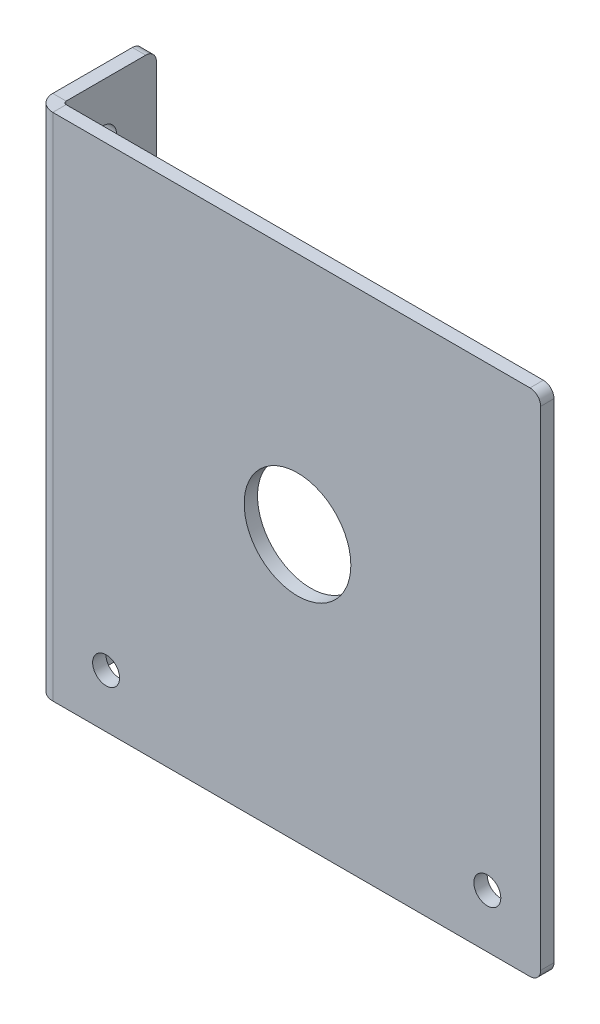
SolidWorks part; units mm, degrees
note: The reader was unsure of these and kept them because the rebuilt part matched: flange length of "Edge-Flange1".
ref_plane "Front Plane" through (0, 0, 0) normal (1, 0, 0) x (0, 1, 0)
ref_plane "Top Plane" through (0, 0, 0) normal (0, 0, 1) x (0, 1, 0)
ref_plane "Right Plane" through (0, 0, 0) normal (0, 1, 0) x (-1, 0, 0)
sketch "Sketch1" plane through (0, 0, 0) normal (0, 0, 1) x (0, 1, 0)
  line L0 (-32.5, 32.5) -> (-63.5, 32.5) construction
  line L1 (-63.5, 62.1879) -> (57.9, 62.1879)
  line L2 (-63.5, 62.1879) -> (-63.5, -57.9)
  line L3 (-63.5, -57.9) -> (57.9, -57.9)
  line L4 (57.9, 62.1879) -> (57.9, -57.9)
  line L5 (32.5, -32.5) -> (32.5, -57.9) construction
  line L6 (32.5, 32.5) -> (32.5, 57.9) construction
  line L7 (57.9, 57.9) -> (-63.5, 57.9) construction
  line L8 (0, 0) -> (32.5, 0) construction
  line L9 (-32.5, 32.5) -> (32.5, 32.5) construction
  line L11 (-32.5, -32.5) -> (32.5, -32.5) construction
  line L12 (32.5, 32.5) -> (32.5, -32.5) construction
  line L13 (-32.5, 32.5) -> (32.5, -32.5) construction
  line L14 (-32.5, -32.5) -> (32.5, 32.5) construction
  line L15 (-32.5, -32.5) -> (-63.5, -32.5) construction
  circle A0 centre (0, 0) radius 12.7
  point P0 (0, 0)
  dimension "D3" = 25.4
  dimension "D1" = 32.5
  dimension "D2" = 4.2879
  dimension "D4" = 63.5
  dimension "D5" = 25.4
  dimension "D6" = 25.4
  dimension "D7" = 25.4
base flange "Base-Flange1" sketch "Sketch1" thickness 3.175 reverse thickness direction yes parameters "D1"=0.7366
edge flange "Edge-Flange1" sketch "Sketch8" flange angle 90 flange length 25.4 flange position material inside bend radius 0.7366 thickness 3.175 relief rectangular parameters "D6"=10
sketch "Sketch8" plane through (-62.1879, 0, 0) normal (-1, 0, 0) x (0, 1, 0)
  line L0 (57.9, 0) -> (-63.5, 0) construction
  line L1 (57.9, 0) -> (-63.5, 0)
  line L2 (-63.5, 0) -> (-63.5, 22.225)
  line L3 (-63.5, 22.225) -> (57.9, 22.225)
  line L4 (57.9, 22.225) -> (57.9, 0)
bend "EdgeBend1" bend radius 0.7366 bend angle 90 parameters "D5"=1
fillet "Fillet1" radius 2.54 4 edges at (57.9, 57.9, 1.5875) (-60.6004, -63.5, -22.225) (-60.6004, 57.9, -22.225) (57.9, -63.5, 1.5875)
sketch "Sketch9" plane through (-59.0129, 0, 0) normal (1, 0, 0) x (0, 1, 0)
  line L0 (-38.1, -0.7366) -> (-38.1, -22.225) construction
  line L1 (-63.5, -0.7366) -> (57.9, -0.7366) construction
  line L4 (-25.4, -9.525) -> (-38.1, -9.525) construction
  line L8 (55.36, -22.225) -> (-60.96, -22.225) construction
  line L9 (45.2, -9.525) -> (57.9, -9.525) construction
  line L10 (57.9, -0.7366) -> (57.9, -19.685) construction
  line L12 (-63.5, -19.685) -> (-63.5, -0.7366) construction
  circle A0 centre (45.2, -9.525) radius 3.205
  circle A1 centre (-25.4, -9.525) radius 3.205
  dimension "D3" = 6.41
  dimension "D1" = 12.7
  dimension "D2" = 12.7
  dimension "D4" = 25.4
extrude "Lower T-Slot Holes" cut sketch "Sketch9" against normal through all normal cut yes
sketch "Sketch10" plane through (0, 0, 0) normal (0, 0, -1) x (1, 0, 0)
  line L0 (45.2, 50.8) -> (57.9, 50.8) construction
  line L2 (57.9, 60.96) -> (57.9, -55.36) construction
  line L4 (57.9, -55.36) -> (57.9, 60.96)
  line L5 (55.36, 63.5) -> (-58.2763, 63.5)
  line L6 (-58.2763, 63.5) -> (-58.2763, -57.9)
  line L7 (-58.2763, -57.9) -> (55.36, -57.9)
  line L8 (57.9, 22.1937) -> (57.9, 28.6063) construction
  line L10 (-58.2763, 28.6063) -> (-58.2763, 22.1937) construction
  line L12 (-45.5763, 50.8) -> (-58.2763, 50.8) construction
  line L13 (-58.2763, -57.9) -> (-58.2763, 63.5) construction
  line L14 (-45.5763, 50.8) -> (45.2, 50.8) construction
  line L15 (-58.2763, 63.5) -> (55.36, 63.5) construction
  circle A0 centre (-45.5763, 50.8) radius 3.2063
  circle A1 centre (45.2, 50.8) radius 3.2063
  arc A2 (57.9, 60.96) -> (55.36, 63.5) centre (55.36, 60.96) ccw
  arc A3 (55.36, -57.9) -> (57.9, -55.36) centre (55.36, -55.36) ccw
  dimension "D3" = 12.7
  dimension "D4" = 12.7
  dimension "D1" = 0
extrude "Upper T-Slot Holes" cut sketch "Sketch10" against normal through all normal cut yes
sketch "Bend-Lines1" [suppressed] plane through (0, 0, 0) normal (0, 1, 0) x (1, 0, 0)
sketch "Bounding-Box1" [suppressed] plane through (0, 0, 0) normal (0, 1, 0) x (1, 0, 0)
sheet metal parameters "Sheet-Metal1" thickness 3.175 parameters "D1"=0.7366
flat pattern "Flat-Pattern1" [suppressed]
sketch "Bend-Lines2" plane through (0, 0, 0) normal (0, 1, 0) x (1, 0, 0)
sketch3d "Bounding-Box2" [suppressed]
  line L0 (-38.1, -38.1, 0) -> (38.1, -38.1, 0) construction
  line L1 (-38.1, 38.1, 0) -> (38.1, 38.1, 0) construction
  line L2 (-38.1, -38.1, 0) -> (-38.1, 38.1, 0) construction
  line L3 (38.1, -38.1, 0) -> (38.1, 38.1, 0) construction
sheet metal parameters "Sheet-Metal2" thickness 3.175 parameters "D1"=0.7366
flat pattern "Flat-Pattern1"
sketch "Bend-Lines2" plane through (0, 0, 0) normal (0, 0, -1) x (-1, 0, 0)
  line L0 (36.0137, -38.1) -> (36.0137, 38.1) construction
  line L1 (36.0137, -38.1) -> (36.0137, 38.1) construction
sketch3d "Bounding-Box2" [suppressed]
  line L0 (59.3275, -38.1, 0) -> (-38.1, -38.1, 0) construction
  line L1 (59.3275, 38.1, 0) -> (-38.1, 38.1, 0) construction
  line L2 (59.3275, -38.1, 0) -> (59.3275, 38.1, 0) construction
  line L3 (-38.1, -38.1, 0) -> (-38.1, 38.1, 0) construction
bend of the flat pattern "Flatten-<EdgeBend1>1"
sheet metal parameters "Sheet-Metal3" thickness 3.175 parameters "D1"=0.7366
flat pattern "Flat-Pattern1"
sketch "Bend-Lines2" plane through (0, 0, 0) normal (0, 0, -1) x (-1, 0, 0)
  line L0 (36.0137, -38.1) -> (36.0137, 38.1) construction
  line L1 (36.0137, -38.1) -> (36.0137, 38.1) construction
sketch3d "Bounding-Box2" [suppressed]
  line L0 (59.3275, -38.1, 0) -> (-38.1, -38.1, 0) construction
  line L1 (59.3275, 38.1, 0) -> (-38.1, 38.1, 0) construction
  line L2 (59.3275, -38.1, 0) -> (59.3275, 38.1, 0) construction
  line L3 (-38.1, -38.1, 0) -> (-38.1, 38.1, 0) construction
bend of the flat pattern "Flatten-<EdgeBend1>1"
sheet metal parameters "Sheet-Metal5" thickness 3.175 parameters "D1"=0.7366
flat pattern "Flat-Pattern1"
sketch "Bend-Lines2" plane through (0, 0, 0) normal (0, 0, -1) x (-1, 0, 0)
  line L0 (60.1017, -63.5) -> (60.1017, 57.9) construction
  line L1 (60.1017, -63.5) -> (60.1017, 57.9) construction
sketch3d "Bounding-Box2" [suppressed]
  line L0 (83.4154, -63.5, 0) -> (-57.9, -63.5, 0) construction
  line L1 (83.4154, 57.9, 0) -> (-57.9, 57.9, 0) construction
  line L2 (83.4154, -63.5, 0) -> (83.4154, 57.9, 0) construction
  line L3 (-57.9, -63.5, 0) -> (-57.9, 57.9, 0) construction
bend of the flat pattern "Flatten-<EdgeBend1>1"
